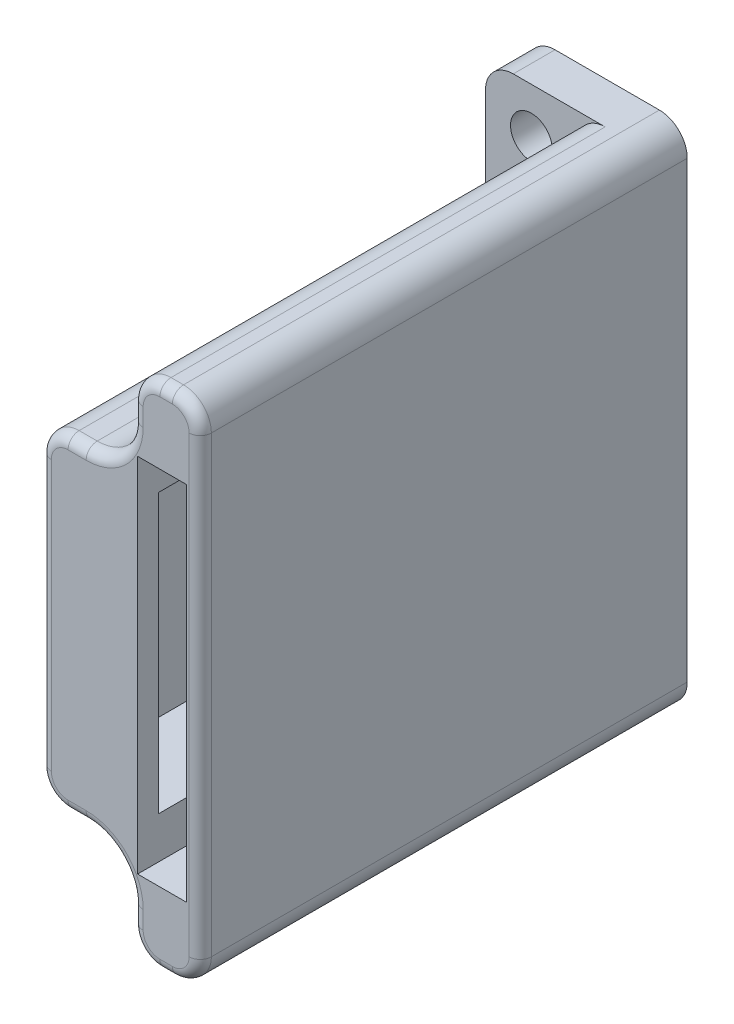
SolidWorks part; units mm, degrees
ref_plane "Front Plane" through (0, 0, 0) normal (0, 0, 1) x (1, 0, 0)
ref_plane "Top Plane" through (0, 0, 0) normal (0, 1, 0) x (1, 0, 0)
ref_plane "Right Plane" through (0, 0, 0) normal (1, 0, 0) x (0, 0, -1)
sketch "Sketch1" plane through (0, 0, 0) normal (0, 0, 1) x (1, 0, 0)
  line L0 (4.191, 46.482) -> (4.191, 42.291) construction
  line L1 (0, 0) -> (14.605, 0)
  line L2 (0, 0) -> (0, 46.482)
  line L3 (0, 46.482) -> (14.605, 46.482)
  line L4 (14.605, 0) -> (14.605, 46.482)
  line L5 (4.191, 0) -> (4.191, 4.191) construction
  circle A0 centre (4.191, 42.291) radius 1.905
  circle A1 centre (4.191, 4.191) radius 1.905
  dimension "D4" = 3.81
  dimension "D1" = 14.605
  dimension "D2" = 4.191
  dimension "D3" = 4.191
  dimension "D5" = 38.1
extrude "Boss-Extrude1" add sketch "Sketch1" along normal blind 44.45
sketch "Sketch2" plane through (0, 0, 44.45) normal (0, 0, 1) x (1, 0, 0)
  line L0 (14.605, 23.241) -> (13.335, 23.241) construction
  line L1 (13.335, 39.751) -> (8.89, 39.751)
  line L2 (13.335, 39.751) -> (13.335, 6.731)
  line L3 (13.335, 6.731) -> (8.89, 6.731)
  line L4 (8.89, 39.751) -> (8.89, 6.731)
  line L5 (14.605, 0) -> (14.605, 46.482) construction
  dimension "D1" = 33.02
  dimension "D2" = 4.445
  dimension "D3" = 1.27
extrude "Cut-Extrude1" cut sketch "Sketch2" against normal blind 38.1
sketch "Sketch3" plane through (13.335, 0, 0) normal (-1, 0, 0) x (0, 0, 1)
  line L0 (0, 46.482) -> (0, 0) construction
  line L1 (0, 35.941) -> (42.545, 35.941)
  line L2 (0, 35.941) -> (0, 10.541)
  line L3 (0, 10.541) -> (42.545, 10.541)
  line L4 (42.545, 35.941) -> (42.545, 10.541)
  line L5 (44.45, 23.241) -> (42.545, 23.241) construction
  line L6 (44.45, 46.482) -> (44.45, 0) construction
  dimension "D1" = 1.905
  dimension "D2" = 25.4
extrude "Cut-Extrude2" cut sketch "Sketch3" along normal offset from surface (12.065 mm away) 1.27 up to face at (0, 23.241, 22.225)
sketch "Sketch4" plane through (0, 0, 44.45) normal (0, 0, 1) x (1, 0, 0)
  line L0 (0, 46.482) -> (0, 0) construction
  line L1 (4.191, 38.1) -> (0, 38.1)
  line L2 (8.382, 42.291) -> (8.382, 46.482)
  line L3 (14.605, 46.482) -> (0, 46.482) construction
  line L4 (4.191, 8.382) -> (0, 8.382)
  line L5 (8.382, 4.191) -> (8.382, 0)
  line L6 (0, 0) -> (14.605, 0) construction
  line L7 (0, 38.1) -> (0, 46.482)
  line L8 (0, 46.482) -> (8.382, 46.482)
  line L9 (0, 8.382) -> (0, 0)
  line L10 (0, 0) -> (8.382, 0)
  arc A0 (4.191, 38.1) -> (8.382, 42.291) centre (4.191, 42.291) ccw
  arc A1 (8.382, 4.191) -> (4.191, 8.382) centre (4.191, 4.191) ccw
extrude "Cut-Extrude3" cut sketch "Sketch4" against normal blind 40.64
fillet "Fillet1" radius 2.54 8 edges at (8.382, 46.482, 24.13) (0, 38.1, 24.13) (0, 8.382, 24.13) (8.382, 0, 24.13) (0, 0, 1.905) (14.605, 0, 22.225) (14.605, 46.482, 22.225) (0, 46.482, 1.905)
fillet "Fillet2" radius 1.016 16 edges at (0.7439, 37.3561, 44.45) (3.3655, 38.1, 44.45) (7.1545, 39.3275, 44.45) (8.382, 43.1165, 44.45) (9.1259, 45.7381, 44.45) (11.4935, 46.482, 44.45) (13.8611, 45.7381, 44.45) (14.605, 23.241, 44.45) (13.8611, 0.7439, 44.45) (11.4935, 0, 44.45) (9.1259, 0.7439, 44.45) (8.382, 3.3655, 44.45) (7.1545, 7.1545, 44.45) (3.3655, 8.382, 44.45) (0.7439, 9.1259, 44.45) (0, 23.241, 44.45)
chamfer "Chamfer1" distance 7.62 angle 45 1 edges at (1.27, 23.241, 42.545)
